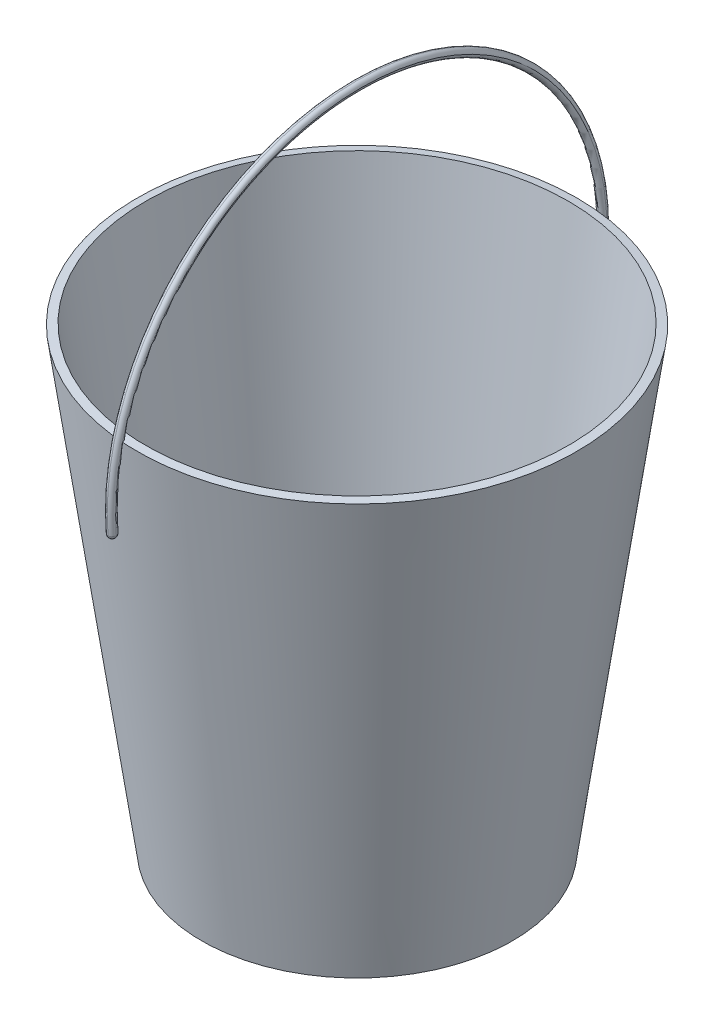
SolidWorks part; units mm, degrees
ref_plane "Front Plane" through (0, 0, 0) normal (0, 0, 1) x (1, 0, 0)
ref_plane "Top Plane" through (0, 0, 0) normal (0, 1, 0) x (1, 0, 0)
ref_plane "Right Plane" through (0, 0, 0) normal (1, 0, 0) x (0, 0, -1)
sketch "Sketch1" plane through (0, 0, 0) normal (0, 0, 1) x (1, 0, 0)
  line L0 (0, 0) -> (0, 51.8219) construction
  line L1 (0, -55) -> (0, 55) construction
  line L2 (0, 0) -> (37.5, 0)
  line L3 (55, 0) -> (-55, 0) construction
  line L4 (37.5, 0) -> (53, 110)
  line L5 (0, 2) -> (35.7621, 2)
  line L6 (35.7621, 2) -> (51.0196, 110.2791)
  line L7 (0, 2) -> (0, 0)
  line L8 (51.0196, 110.2791) -> (53, 110)
  dimension "D1" = 75
  dimension "D2" = 110
  dimension "D3" = 106
  dimension "D4" = 2
revolve "Revolve1" add sketch "Sketch1" angle 360 about L0
sketch "Sketch2" plane through (0, 0, 0) normal (1, 0, 0) x (0, 0, -1)
  line L0 (58.3, 0) -> (-58.3, 0) construction
  line L1 (53, 110) -> (-53, 110) construction
  line L2 (-59, 95) -> (59, 95) construction
  arc A0 (-59, 95) -> (59, 95) centre (0, 100.7231) cw
  point P3 (0, 160)
  dimension "D1" = 160
  dimension "D2" = 15
  dimension "D3" = 6
  dimension "D4" = 6
extrude "Extrude-Thin1" add sketch "Sketch2" along normal mid plane 2 thin thin type mid plane wall 2
fillet "Fillet1" radius 1 4 edges at (-1, 159, 0) (1, 159, 0) (1, 161, 0) (-1, 161, 0)
